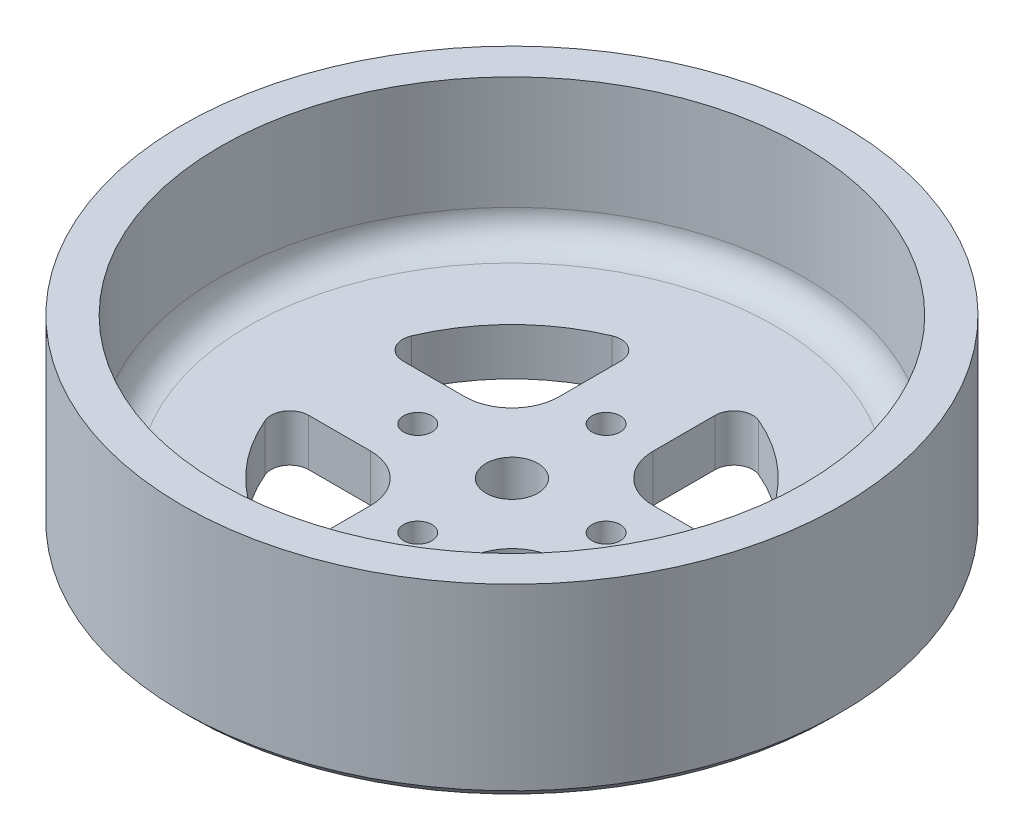
SolidWorks part; units mm, degrees
material "三聚氰胺甲醛树脂"
ref_plane "前视基准面" through (0, 0, 0) normal (0, 0, 1) x (1, 0, 0)
ref_plane "上视基准面" through (0, 0, 0) normal (0, 1, 0) x (1, 0, 0)
ref_plane "右视基准面" through (0, 0, 0) normal (1, 0, 0) x (0, 0, -1)
sketch "草图1" plane through (0, 0, 0) normal (0, 1, 0) x (1, 0, 0)
  line L0 (-19.3649, 5) -> (-5, 5)
  line L1 (-5, 5) -> (-5, 19.3649)
  line L2 (5, 19.3649) -> (5, 5)
  line L3 (5, 5) -> (19.3649, 5)
  line L4 (19.3649, -5) -> (5, -5)
  line L5 (5, -5) -> (5, -19.3649)
  line L6 (-5, -19.3649) -> (-5, -5)
  line L7 (-5, -5) -> (-19.3649, -5)
  circle A0 centre (0, 0) radius 1.25
  circle A1 centre (0, 0) radius 31
  circle A2 centre (0, 0) radius 35
  circle A3 centre (0, 0) radius 2.75
  circle A4 centre (-10, 0) radius 1.5
  circle A5 centre (0, 10) radius 1.5
  circle A6 centre (10, 0) radius 1.5
  circle A7 centre (0, -10) radius 1.5
  arc A8 (-5, 19.3649) -> (-19.3649, 5) centre (0, 0) ccw
  arc A9 (19.3649, 5) -> (5, 19.3649) centre (0, 0) ccw
  arc A10 (-19.3649, -5) -> (-5, -19.3649) centre (0, 0) ccw
  arc A11 (5, -19.3649) -> (19.3649, -5) centre (0, 0) ccw
  point P17 (0, 0)
  point P31 (0, 0)
  dimension "D1" = 5.5
  dimension "D2" = 2.5
  dimension "D3" = 4
  dimension "D4" = 70
  dimension "D5" = 3
  dimension "D6" = 10
  dimension "D8" = 40
  dimension "D10" = 10
  dimension "D7" = 4
  dimension "D9" = 4
extrude "凸台-拉伸1" add sketch "草图1" along normal blind 5 contours A1 A11 L5 L4 A10 L7 L6 A9 L3 L2 A8 L1 L0 A7 A6 A5 A4 A3 region at (-30.1232, 0, 0)
extrude "凸台-拉伸3" add sketch "草图1<4>" along normal blind 20 contours A2 A1 region at (-34.0101, 0, 0)
sketch "草图1<4>" plane through (0, 0, 0) normal (0, 1, 0) x (1, 0, 0) same geometry as "草图1"
fillet "圆角1" radius 5 4 edges at (-5, 2.5, 5) (5, 2.5, 5) (5, 2.5, -5) (-5, 2.5, -5)
fillet "圆角2" radius 2 8 edges at (5, 2.5, 19.3649) (19.3649, 2.5, 5) (19.3649, 2.5, -5) (5, 2.5, -19.3649) (-5, 2.5, 19.3649) (-19.3649, 2.5, 5) (-5, 2.5, -19.3649) (-19.3649, 2.5, -5)
chamfer "倒角1" distance 1 angle 45 1 edges at (0, 0, 35)
fillet "圆角3" radius 3 1 edges at (0, 5, 31)
